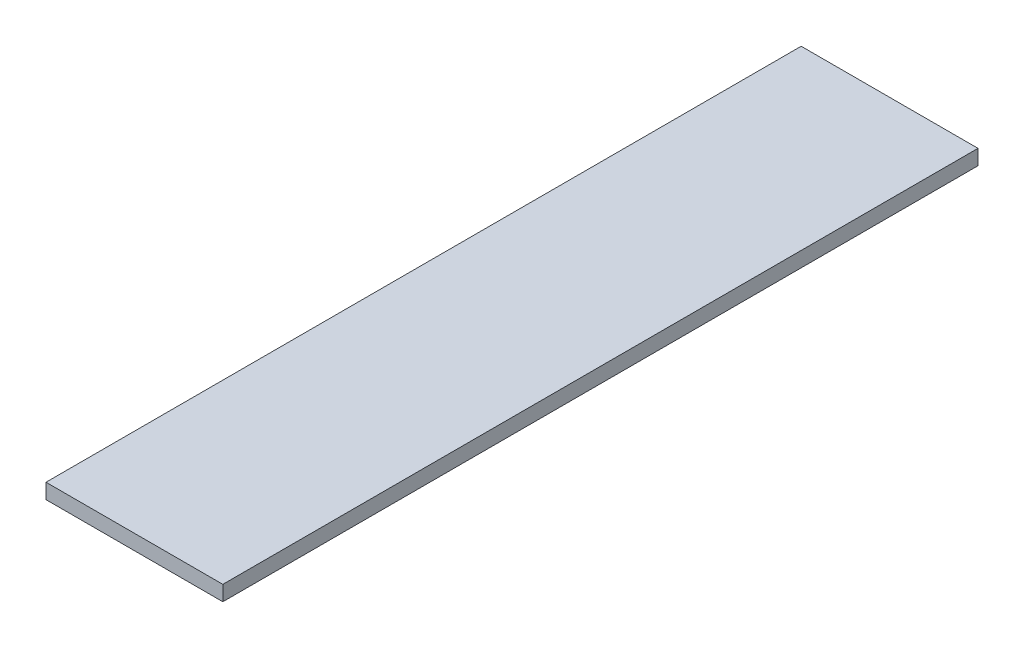
SolidWorks part; units mm, degrees
material "Copper"
ref_plane "Front Plane" through (0, 0, 0) normal (0, 0, 1) x (1, 0, 0)
ref_plane "Top Plane" through (0, 0, 0) normal (0, 1, 0) x (1, 0, 0)
ref_plane "Right Plane" through (0, 0, 0) normal (1, 0, 0) x (0, 0, -1)
sketch "Sketch1" plane through (0, 0, 0) normal (0, 0, 1) x (1, 0, 0)
  line L4 (-5.8542, 55.6986) -> (-5.8542, 56.6986)
  line L5 (28.0027, 48.5021) -> (17.3066, 53.2643)
  line L6 (17.3066, 53.2643) -> (5.8542, 55.6986)
  line L7 (5.8542, 55.6986) -> (-5.8542, 55.6986)
  line L8 (-5.8542, 55.6986) -> (-17.3066, 53.2643)
  line L9 (-17.3066, 53.2643) -> (-28.0027, 48.5021)
  line L10 (-28.0027, 48.5021) -> (-37.4749, 41.6201)
  line L11 (-37.4749, 41.6201) -> (-45.3093, 32.9191)
  line L12 (-45.3093, 32.9191) -> (-51.1635, 22.7794)
  line L13 (-51.1635, 22.7794) -> (-54.7815, 11.6442)
  line L14 (-54.7815, 11.6442) -> (-56.0054, 0)
  line L15 (-56.0054, 0) -> (-54.7815, -11.6442)
  line L16 (-54.7815, -11.6442) -> (-51.1635, -22.7794)
  line L17 (-51.1635, -22.7794) -> (-45.3093, -32.9191)
  line L18 (-45.3093, -32.9191) -> (-37.4749, -41.6201)
  line L19 (-37.4749, -41.6201) -> (-28.0027, -48.5021)
  line L20 (-28.0027, -48.5021) -> (-17.3066, -53.2643)
  line L21 (-17.3066, -53.2643) -> (-5.8542, -55.6986)
  line L22 (-5.8542, -55.6986) -> (5.8542, -55.6986)
  line L23 (5.8542, -55.6986) -> (17.3066, -53.2643)
  line L24 (17.3066, -53.2643) -> (28.0027, -48.5021)
  line L25 (28.0027, -48.5021) -> (37.4749, -41.6201)
  line L26 (37.4749, -41.6201) -> (45.3093, -32.9191)
  line L27 (45.3093, -32.9191) -> (51.1635, -22.7794)
  line L28 (51.1635, -22.7794) -> (54.7815, -11.6442)
  line L29 (54.7815, -11.6442) -> (56.0054, 0)
  line L30 (56.0054, 0) -> (54.7815, 11.6442)
  line L31 (54.7815, 11.6442) -> (51.1635, 22.7794)
  line L32 (51.1635, 22.7794) -> (45.3093, 32.9191)
  line L33 (45.3093, 32.9191) -> (37.4749, 41.6201)
  line L34 (37.4749, 41.6201) -> (28.0027, 48.5021)
  line L35 (-5.8542, 56.6986) -> (5.8542, 56.6986)
  line L36 (5.8542, 56.6986) -> (5.8542, 55.6986)
  circle A1 centre (0, 0) radius 55.6986 construction
  dimension "D1" = 1
  dimension "D2" = 57
extrude "Boss-Extrude1" add sketch "Sketch1" along normal mid plane 50 contours L36 L35 L4 L7 region at (0, 56.1986, 0)
